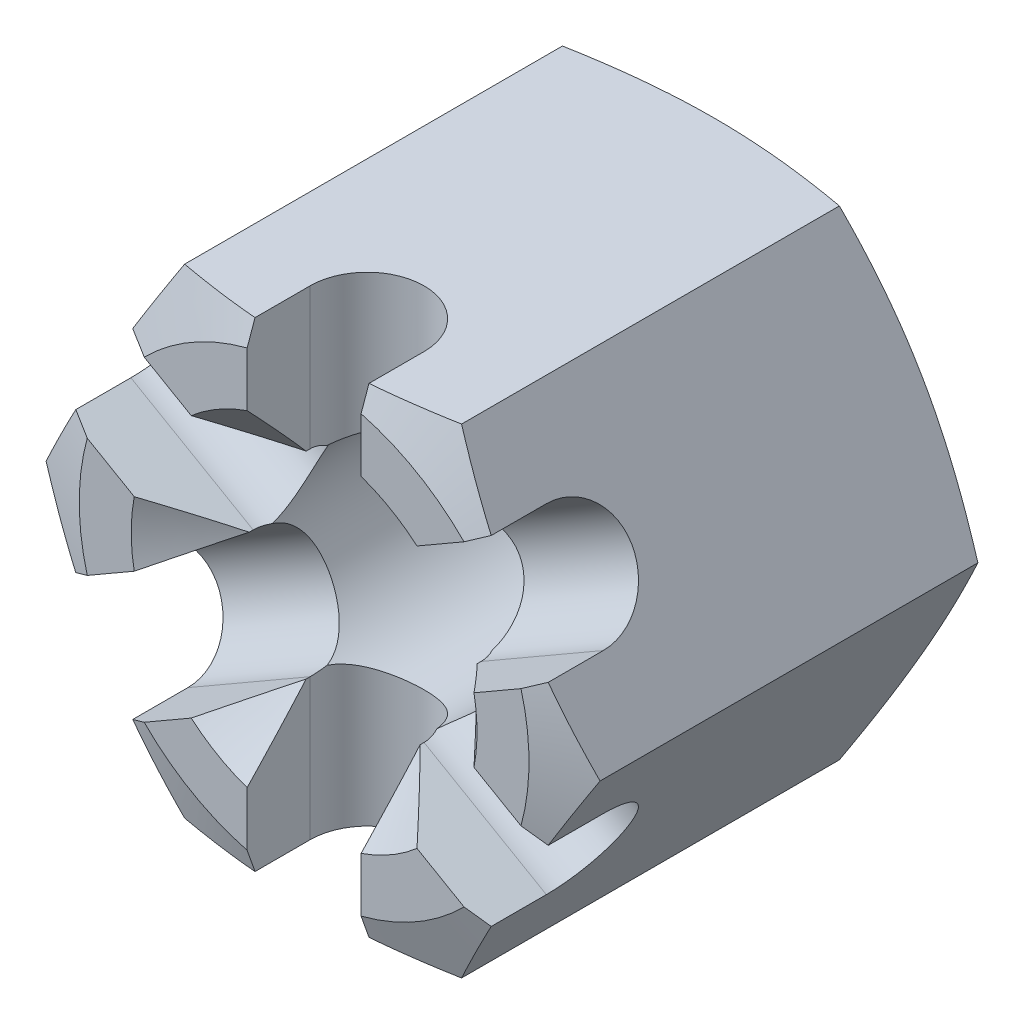
SolidWorks part; units mm, degrees
ref_plane "Front" through (0, 0, 0) normal (0, 0, 1) x (1, 0, 0)
ref_plane "Top" through (0, 0, 0) normal (0, 1, 0) x (1, 0, 0)
ref_plane "Right" through (0, 0, 0) normal (1, 0, 0) x (0, 0, -1)
sketch "Sketch1" plane through (0, 0, 0) normal (0, 0, 1) x (1, 0, 0)
  line L1 (6.9282, -12) -> (13.8564, 0)
  line L2 (13.8564, 0) -> (6.9282, 12)
  line L3 (6.9282, 12) -> (-6.9282, 12)
  line L4 (-6.9282, 12) -> (-13.8564, 0)
  line L5 (-13.8564, 0) -> (-6.9282, -12)
  line L6 (-6.9282, -12) -> (6.9282, -12)
  circle A0 centre (0, 0) radius 12 construction
  dimension "s" = 24
extrude "BaseNut" add sketch "Sketch1" against normal blind 20.8
sketch "Sketch2" plane through (-3.4718, 0, -17.3282) normal (0, 1, 0) x (0, 0, -1)
  line L0 (3.4718, 7.7782) -> (2.5231, 10.3846)
  line L3 (2.5231, 10.3846) -> (3.4718, 10.3846)
  line L4 (3.4718, 10.3846) -> (3.4718, 7.7782)
  line L5 (0, -3.4718) -> (-12.6262, -3.4718) construction
  line L6 (-17.3282, 7.7782) -> (-17.3282, 10.3846)
  line L8 (-17.3282, 10.3846) -> (-16.3795, 10.3846)
  line L9 (-16.3795, 10.3846) -> (-17.3282, 7.7782)
  dimension "dw" = 22.5
  dimension "D2" = 20
  dimension "D3" = 20
revolve "Double-Chamfer" cut sketch "Sketch2" angle 360 about L5
sketch "Sketch3" plane through (2.6208, -2.2475, -20.8) normal (0, 0, -1) x (-1, 0, 0)
  line L0 (2.6208, 2.2475) -> (2.6208, 3.7475) construction
  circle A0 centre (2.6208, 2.2475) radius 5.5
  circle A1 centre (2.6208, 2.2475) radius 11.25 construction
  dimension "D1" = 11
  dimension "D2" = 1.5
extrude "Hole" cut sketch "Sketch3" against normal through all
cosmetic thread "ThreadCosmetic1" [suppressed] parameters "D2"=14
sketch "Sketch4" plane through (-15.7583, 0, -7.1083) normal (0, 1, 0) x (0, 0, -1)
  line L0 (13.6917, -24.4083) -> (10.5417, -21.2583)
  line L2 (10.5417, -21.2583) -> (13.6917, -21.2583)
  line L3 (13.6917, -21.2583) -> (13.6917, -24.4083)
  line L4 (0, -15.7583) -> (-22.8666, -15.7583) construction
  line L7 (-7.1083, -21.2583) -> (-3.9583, -21.2583)
  line L9 (-3.9583, -21.2583) -> (-7.1083, -24.4083)
  line L10 (-7.1083, -24.4083) -> (-7.1083, -21.2583)
  dimension "D1" = 17.3
  dimension "D2" = 45
  dimension "D3" = 45
revolve "EndChamfer" cut sketch "Sketch4" angle 360 about L4
sketch "Sketch5" plane through (-17.8, 0, -17.8) normal (0, 1, 0) x (0, 0, -1)
  line L0 (-17.8, -14.95) -> (-14.65, -14.95)
  line L2 (-14.65, -20.65) -> (-17.8, -20.65)
  line L3 (-17.8, -20.65) -> (-17.8, -14.95)
  line L5 (-10.6917, -17.8) -> (-33.5583, -17.8) construction
  line L6 (-14.65, -17.8) -> (-0.15, -17.8) construction
  line L7 (3, -26.45) -> (3, -9.15) construction
  line L14 (-17.8, -9.15) -> (-17.8, -26.45) construction
  arc A0 (-14.65, -14.95) -> (-14.65, -20.65) centre (-14.65, -17.8) cw
  point P6 (-11.8, -17.8)
  point P9 (3, -17.8)
  dimension "n" = 5.7
  dimension "W" = 14.8
extrude "Slot" cut sketch "Sketch5" against normal through all
pattern_circular "SlotPattern" count 6 over 360 about axis through (0, 0, 0) along (0, 0, -1) of "Slot"
sketch "Sketch7" plane through (0, 0, 0) normal (0, 1, 0) x (1, 0, 0)
  line L0 (0, 23.693) -> (0, 15.0456) construction
  line L1 (4, 18.4) -> (5.5, 18.4)
  line L2 (5.5, 18.4) -> (6.799, 17.65)
  line L3 (6.799, 17.65) -> (5.5, 16.9)
  line L4 (5.5, 16.9) -> (4, 16.9)
  line L5 (4, 16.9) -> (4, 18.4)
  line L6 (-5.5, 17.65) -> (5.5, 17.65) construction
  dimension "D1" = 1.5
  dimension "D2" = 11
revolve "Cut-Revolve10" [suppressed] cut sketch "Sketch7" angle 360 about L0
pattern_linear "LPattern10" [suppressed] count 10 spacing 1.8 along (0, 0, 1) of bodies 108
equation "\"D1@Sketch3\" = \"D2@ThreadCosmetic1\" - \"D2@Sketch3\" * 2"
equation "\"D2@Sketch7\" = \"D1@Sketch3\""
equation "\"D1@Sketch7\" = (  \"D2@ThreadCosmetic1\" - \"D1@Sketch3\" )  / 2"
equation "\"D3@LPattern10\" = \"D1@Sketch7\" * 1.2"
equation "\"D1@LPattern10\" =  ( \"m@BaseNut\" -  (  \"D1@Sketch4\" - \"D2@Sketch7\")  / 2  ) / \"D3@LPattern10\" "
